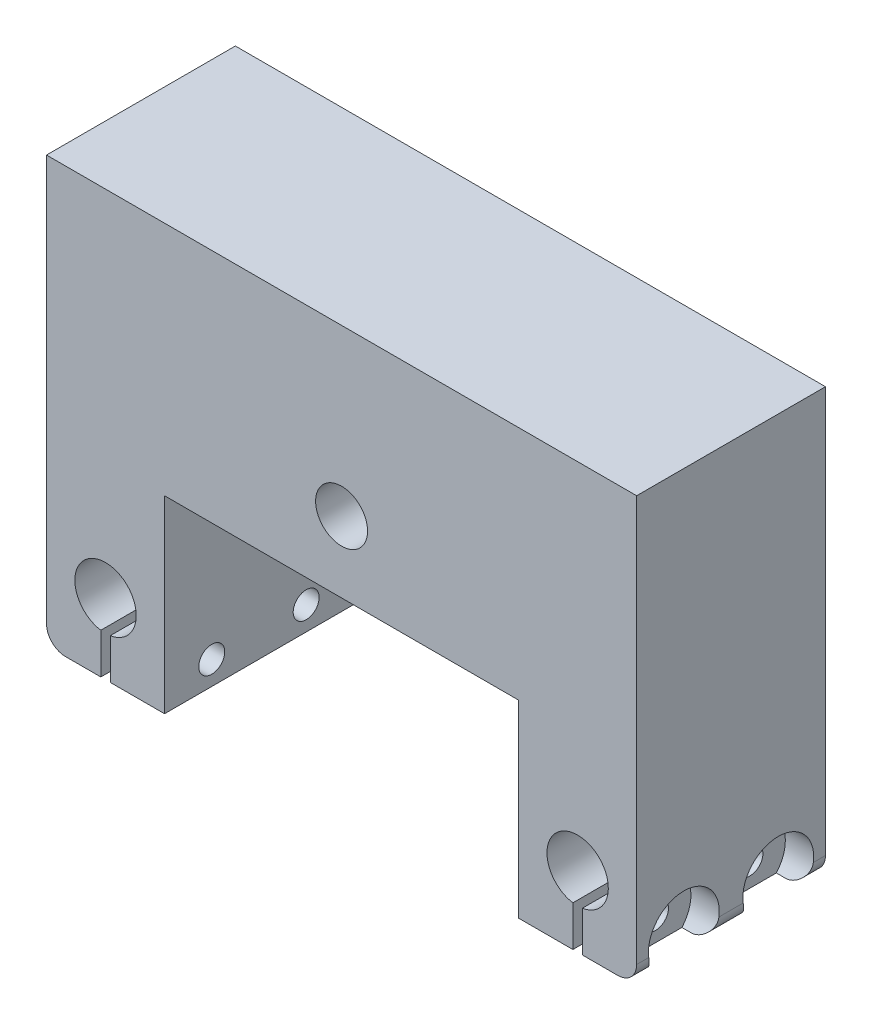
SolidWorks part; units mm, degrees
ref_plane "Front Plane" through (0, 0, 0) normal (0, 0, 1) x (1, 0, 0)
ref_plane "Top Plane" through (0, 0, 0) normal (0, 1, 0) x (1, 0, 0)
ref_plane "Right Plane" through (0, 0, 0) normal (1, 0, 0) x (0, 0, -1)
sketch "Sketch1" plane through (0, 0, 0) normal (0, 0, 1) x (1, 0, 0)
  line L1 (-31.25, 0) -> (31.25, 0)
  line L2 (-31.25, 0) -> (-31.25, 45)
  line L3 (-31.25, 45) -> (31.25, 45)
  line L4 (31.25, 0) -> (31.25, 45)
  point P4 (0, 0)
  dimension "D1" = 62.5
  dimension "D2" = 45
extrude "Boss-Extrude1" add sketch "Sketch1" along normal blind 20
sketch "Sketch14" plane through (0, 0, 20) normal (0, 0, 1) x (1, 0, 0)
  line L0 (-31.25, 0) -> (31.25, 0) construction
  line L2 (25, 0) -> (25, 45) construction
  line L3 (-31.25, 0) -> (31.25, 0) construction
  line L4 (25.5, 4.2887) -> (25.5, 0)
  line L5 (25.5, 0) -> (24.5, 0)
  line L6 (24.5, 0) -> (24.5, 4.2887)
  circle A0 centre (25, 7.5) radius 3.25
  point P12 (0, 0)
  line M6 (-31.25, 0) -> (31.25, 0)
  dimension "D1" = 6.5
  dimension "D4" = 25
  dimension "D2" = 7.5
  dimension "D3" = 1
  dimension "D5" = 0.5
extrude "Cut-Extrude10" cut sketch "Sketch14" against normal through all contours L2 A0 | A0 L2 | L2 A0 L6 M6 | L2 L5 L4 A0 region at (24.7496, 2.1314, 20) region at (25.2504, 2.1314, 20) region at (23.6207, 7.5, 20) region at (26.3793, 7.5, 20)
mirror "Mirror1" about plane through (0, 0, 0) normal (1, 0, 0) of "Cut-Extrude10"
sketch "Sketch18" plane through (0, 0, 20) normal (0, 0, 1) x (1, 0, 0)
  line L0 (-24.5, 0) -> (24.5, 0) construction
  line L1 (18.75, 0) -> (-18.75, 0)
  line L2 (18.75, 0) -> (18.75, 20)
  line L3 (18.75, 20) -> (-18.75, 20)
  line L4 (-18.75, 0) -> (-18.75, 20)
  point P6 (0, 0)
  dimension "D1" = 37.5
  dimension "D2" = 20
extrude "Cut-Extrude13" cut sketch "Sketch18" against normal through all
sketch "Sketch19" plane through (0, 0, 20) normal (0, 0, 1) x (1, 0, 0)
  line L0 (18.75, 0) -> (24.5, 0) construction
  circle A0 centre (0, 27.5) radius 2.75
  dimension "D1" = 5.5
  dimension "D2" = 27.5
extrude "Cut-Extrude14" cut sketch "Sketch19" against normal through all
sketch "Sketch20" plane through (31.25, 0, 0) normal (1, 0, 0) x (0, 0, -1)
  line L0 (0, 0) -> (0, 45) construction
  line L1 (-20, 0) -> (0, 0) construction
  line L2 (-20, 0) -> (-20, 45) construction
  circle A0 centre (-5, 2.5) radius 1.375
  circle A1 centre (-15, 2.5) radius 1.375
  dimension "D1" = 2.75
  dimension "D4" = 5
  dimension "D5" = 2.5
  dimension "D2" = 5
  dimension "D3" = 2.5
extrude "Cut-Extrude15" cut sketch "Sketch20" against normal through all
fillet "Fillet1" radius 2 2 edges at (-31.25, 0, 10) (31.25, 0, 10)
sketch "Sketch21" plane through (31.25, 0, 0) normal (1, 0, 0) x (0, 0, -1)
  circle A0 centre (-5, 2.5) radius 3.75
  circle A1 centre (-15, 2.5) radius 3.75
  dimension "D1" = 7.5
extrude "Cut-Extrude16" cut sketch "Sketch21" against normal blind 3
mirror "Mirror2" about plane through (0, 0, 0) normal (1, 0, 0) of "Cut-Extrude16"
